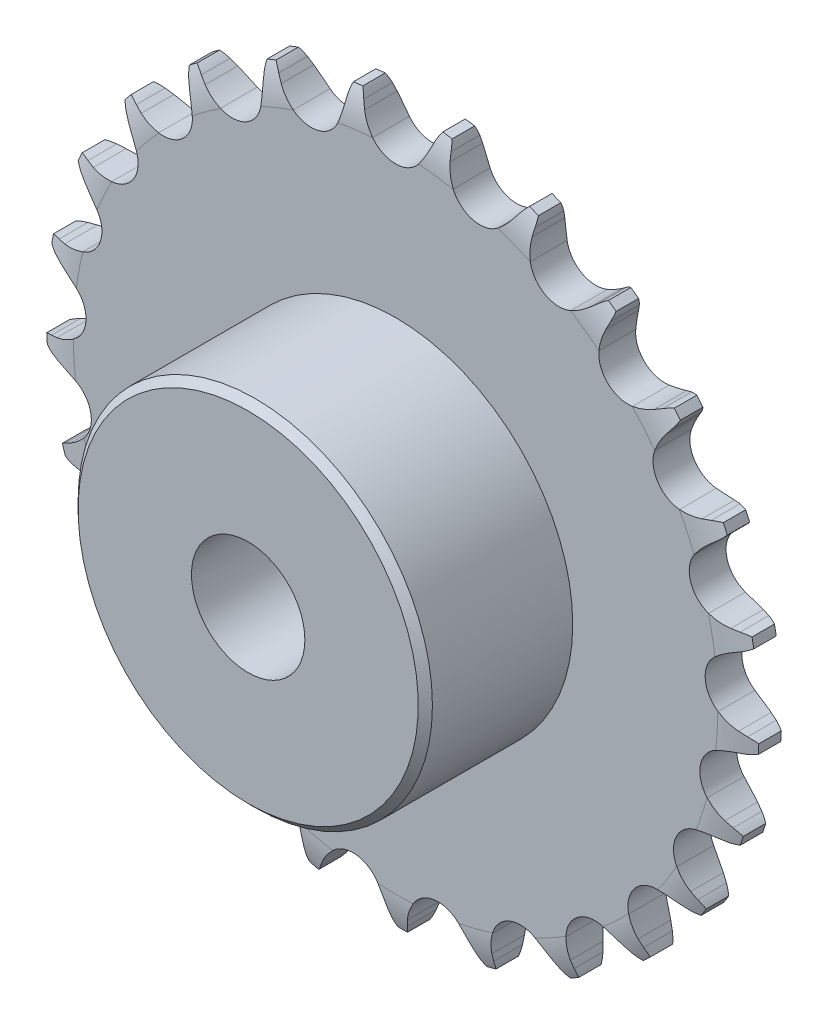
SolidWorks part; units mm, degrees
ref_plane "Front Plane" through (0, 0, 0) normal (0, 0, 1) x (1, 0, 0)
ref_plane "Top Plane" through (0, 0, 0) normal (0, 1, 0) x (1, 0, 0)
ref_plane "Right Plane" through (0, 0, 0) normal (1, 0, 0) x (0, 0, -1)
sketch "Sketch0" plane through (0, 0, 0) normal (0, 0, 1) x (1, 0, 0)
  line L0 (3, -23.7474) -> (0, 0) construction
  line L1 (0, 0) -> (8.8115, -22.2553) construction
  line L2 (0, 0) -> (-3, -23.7474) construction
  line L3 (3, -23.7474) -> (8.8115, -22.2553) construction
  line L4 (3, -23.7474) -> (-3, -23.7474) construction
  line L5 (5.573, -23.9247) -> (5.3187, -23.4628)
  line L6 (3, -23.7474) -> (0, -24.1264) construction
  line L7 (0.5519, -24.5591) -> (0.6834, -24.0484)
  line L8 (0, -23.7474) -> (0, -25.5474) construction
  line L9 (4.4583, -22.3094) -> (0.7215, -25.9943) construction
  line L10 (0, 0) -> (0, -23.7474) construction
  line L11 (5.3187, -23.4628) -> (0.7215, -25.9943) construction
  line L12 (0, -25.5474) -> (0, -25.7053) construction
  line L13 (8.4241, -22.3548) -> (5.573, -23.9247) construction
  circle A0 centre (0, 0) radius 25.5474 construction
  circle A1 centre (0, 0) radius 23.9362 construction
  arc A2 (-2.9542, -26.9828) -> (9.5718, -25.4004) centre (0, 0) ccw
  circle A3 centre (0, 0) radius 25.7053 construction
  circle A4 centre (3, -23.7474) radius 2 construction
  arc A7 (4.4583, -22.3094) -> (1.2299, -22.7172) centre (3, -23.7474) ccw
  circle A8 centre (3, -23.7474) radius 2.0481 construction
  arc A9 (5.573, -23.9247) -> (9.5718, -25.4004) centre (8.4241, -22.3548) ccw
  arc A10 (5.3187, -23.4628) -> (4.4583, -22.3094) centre (0.7215, -25.9943) ccw
  arc A11 (0.5519, -24.5591) -> (-2.9542, -26.9828) centre (-2.6, -23.7474) cw
  arc A12 (0.6834, -24.0484) -> (1.2299, -22.7172) centre (5.7657, -25.3571) cw
  dimension "D1" = 2.0481
  dimension "R" = 2.0481
sketch "Sketch1" plane through (0, 0, 0) normal (1, 0, 0) x (0, 0, -1)
  line L0 (1.3, 0) -> (-1.3, 0)
  line L1 (-1.3, 0) -> (-1.3, 22.735)
  line L2 (-1.3, 23.9362) -> (0, 23.9362) construction
  line L3 (-0.6, 25.5474) -> (0.6, 25.5474)
  line L5 (1.3, 22.735) -> (1.3, 0)
  line L7 (0, 25.5474) -> (0, 0) construction
  line L8 (-1.3, 22.735) -> (1.3, 22.735) construction
  line L9 (0, 25.5474) -> (0, -25.5474) construction
  line L10 (-1.3, 22.735) -> (-1.3, 25.5474) construction
  line L11 (-1.3, 25.5474) -> (-0.6, 25.5474) construction
  line L12 (0.6, 25.5474) -> (1.3, 25.5474) construction
  line L13 (1.3, 25.5474) -> (1.3, 22.735) construction
  line L14 (0, 0) -> (-6.4008, 0) construction
  line L15 (-1.3, 23.9362) -> (-1.3, 19.8362) construction
  line L22 (1.3, 0) -> (-11.7, 0) construction
  line L24 (-1.3, 0) -> (-1.3, 19.8362) construction
  arc A0 (-0.6, 25.5474) -> (-1.3, 22.735) centre (4.7, 22.735) ccw
  arc A1 (0.6, 25.5474) -> (1.3, 22.735) centre (-4.7, 22.735) cw
  dimension "R" = 6
revolve "Revolve1" add sketch "Sketch1" angle 360 mid plane about L0
extrude "Cut-Extrude1" cut sketch "Sketch0" against normal through all and the other way through all
pattern_circular "CirPattern1" count 25 over 360 about axis through (0, 0, -1.3) along (0, 0, -1) of "Cut-Extrude1"
sketch "Sketch2" plane through (0, 0, 0) normal (0, 0, 1) x (1, 0, 0)
  circle A0 centre (0, 0) radius 4 construction
  circle A1 centre (0, 0) radius 12.5
  circle A2 centre (0, 0) radius 25.15 construction
  dimension "Bore" = 8
  dimension "Hub Dia." = 25
  dimension "OD" = 50.3
extrude "Boss-Extrude1" add sketch "Sketch2" along normal up to vertex (11.7 mm away) from surface up to point (0, 0, 11.7) starting at face at (0, 0, 1.3)
sketch "Sketch3" plane through (0, 0, 0) normal (0, 0, 1) x (1, 0, 0)
  circle A0 centre (0, 0) radius 4 construction
  circle A1 centre (0, 0) radius 4
extrude "Cut-Extrude2" cut sketch "Sketch3" along normal through all and the other way through all
sketch "Sketch4" plane through (0, 0, 0) normal (1, 0, 0) x (0, 0, -1)
  line L0 (-11.7, 12.5) -> (-11.7, 12)
  line L1 (-1.3, 25.5474) -> (-3.25, 25.5474)
  line L2 (-1.3, 25.5474) -> (-1.3, 19.8362)
  line L3 (-1.3, 19.8362) -> (-3.25, 19.8362)
  line L4 (-3.25, 25.5474) -> (-3.25, 19.8362)
  line L9 (-11.7, 12) -> (-11.2, 12.5)
  line L10 (-11.2, 12.5) -> (-11.7, 12.5)
  dimension "C" = 0.5
  dimension "D3" = 1.95
revolve "Cut-Revolve1" cut sketch "Sketch4" angle 360 mid plane about L22
sketch "Sketch5" plane through (0, 0, 0) normal (0, 0, 1) x (1, 0, 0)
  circle A0 centre (0, 0) radius 25.15 construction
  circle A1 centre (0, 0) radius 25.15
extrude "Cut-Extrude3" cut sketch "Sketch5" against normal through all and the other way through all flip side to cut
equation "\"360/N@Sketch0\" = 360/\"Teeth@CirPattern1\""
equation "\"Ds@Sketch0\" = 1.005 * \"Dr@Sketch0\" + ( 0.003 * 25.4 ) "
equation "\"R@Sketch0\" = 1/2 * \"Ds@Sketch0\""
equation "\"A@Sketch0\" = 35 +  ( 60 / \"Teeth@CirPattern1\" ) "
equation "\"B@Sketch0\" = 18 -  ( 56 / \"Teeth@CirPattern1\" )"
equation "\"ac@Sketch0\" = 0.8 * \"Dr@Sketch0\""
equation "\"ab@Sketch0\" = 1.4 * \"Dr@Sketch0\""
equation "\"J@Sketch0\" = 0.3 * \"Pitch@Sketch0\""
equation "\"D3@Sketch4\" = \"t@Sketch1\" * 3 / 4"
